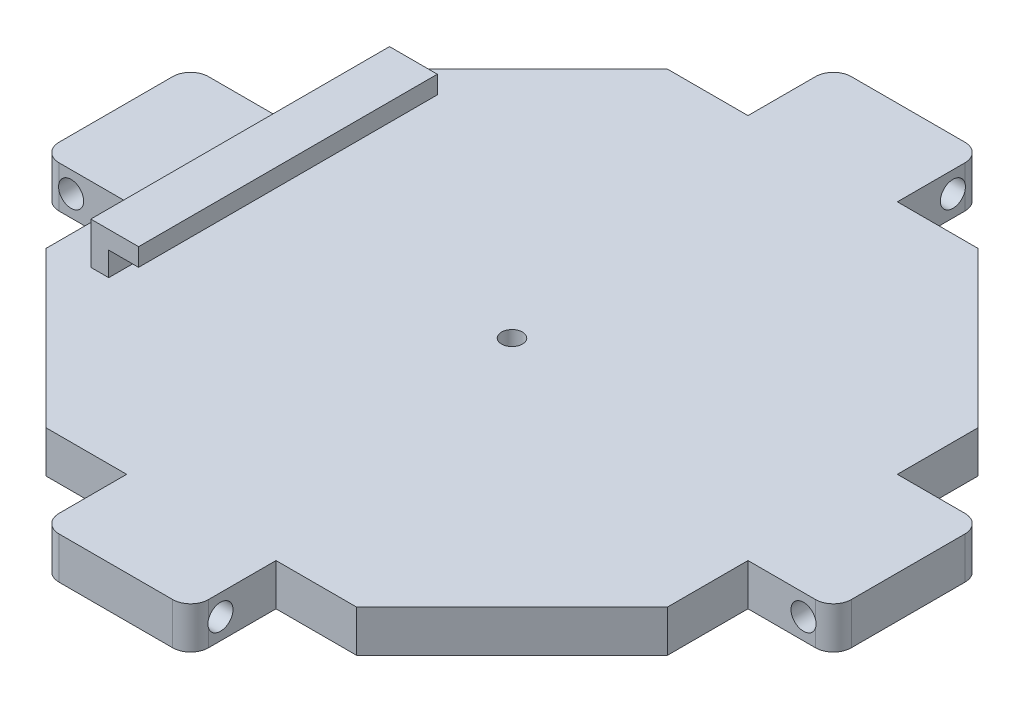
SolidWorks part; units mm, degrees
ref_plane "정면" through (0, 0, 0) normal (0, 0, 1) x (1, 0, 0)
ref_plane "윗면" through (0, 0, 0) normal (0, 1, 0) x (1, 0, 0)
ref_plane "우측면" through (0, 0, 0) normal (1, 0, 0) x (0, 0, -1)
sketch "스케치1" plane through (0, 0, 0) normal (0, 1, 0) x (1, 0, 0)
  line L0 (0, 0) -> (-27.1519, 0) construction
  line L1 (-39, 39) -> (39, 39)
  line L2 (-39, 39) -> (-39, -39)
  line L3 (-39, -39) -> (39, -39)
  line L4 (39, 39) -> (39, -39)
  line L5 (-39, 39) -> (39, -39) construction
  line L6 (-39, -39) -> (39, 39) construction
  line L7 (39, 0) -> (-66.3, 0) construction
  line L8 (-66.3, 0) -> (0, 39) construction
  line L9 (0, 39) -> (0, -39) construction
  line L10 (-26, 39) -> (-39, 26)
  line L11 (-39, -26) -> (-26, -39)
  line L12 (26, -39) -> (39, -26)
  line L13 (26, 39) -> (39, 26)
  line L14 (-26, -52) -> (26, -52)
  line L15 (26, -52) -> (52, -26)
  line L16 (52, -26) -> (52, 26)
  line L17 (52, 26) -> (26, 52)
  line L18 (26, 52) -> (-26, 52)
  line L19 (-26, 52) -> (-52, 26)
  line L20 (-52, 26) -> (-52, -26)
  line L21 (-52, -26) -> (-26, -52)
  line L22 (-52, 12.5) -> (-66.3, 12.5)
  line L23 (-66.3, 12.5) -> (-66.3, -12.5)
  line L24 (-66.3, -12.5) -> (-52, -12.5)
  line L25 (-12.5, -52) -> (-12.5, -66.3)
  line L26 (-12.5, -66.3) -> (12.5, -66.3)
  line L27 (12.5, -66.3) -> (12.5, -52)
  line L28 (52, -12.5) -> (66.3, -12.5)
  line L29 (66.3, -12.5) -> (66.3, 12.5)
  line L30 (66.3, 12.5) -> (52, 12.5)
  line L31 (-12.5, 52) -> (-12.5, 66.3)
  line L32 (-12.5, 66.3) -> (12.5, 66.3)
  line L33 (12.5, 66.3) -> (12.5, 52)
  point P0 (0, 0)
  dimension "D1" = 78
  dimension "D2" = 78
  dimension "D3" = 26
  dimension "D4" = 26
  dimension "D5" = 26
  dimension "D6" = 26
  dimension "D7" = 26
  dimension "D8" = 26
  dimension "D9" = 26
  dimension "D10" = 26
  dimension "D11" = 13
  dimension "D12" = 13
  dimension "D13" = 13
  dimension "D14" = 13
  dimension "D15" = 25
  dimension "D16" = 25
  dimension "D17" = 25
  dimension "D18" = 25
  dimension "D19" = 14.3
  dimension "D20" = 14.3
  dimension "D21" = 14.3
  dimension "D22" = 14.3
  dimension "D23" = 14.3
  dimension "D24" = 12.5
  dimension "D25" = 12.5
  dimension "D26" = 12.5
extrude "보스-돌출1" add sketch "스케치1" along normal blind 7 contours L18 L19 L1 L17 | L10 L1 L2 | L20 L21 L2 L19 | L23 L24 L20 L22 | L33 L32 L31 L18 | L1 L13 L4 | L16 L17 L4 L15 | L29 L30 L16 L28 | L12 L3 L4 | L3 L21 L14 L15 | L11 L2 L3 | L26 L27 L14 L25 region at (0, 0, -45.0667) region at (-34.6667, 0, -34.6667) region at (-45.0667, 0, 0) region at (34.6667, 0, -34.6667) region at (-34.6667, 0, 34.6667) region at (0, 0, -59.15) region at (-59.15, 0, 0) region at (45.0667, 0, 0) region at (0, 0, 45.0667) region at (34.6667, 0, 34.6667) region at (59.15, 0, 0) region at (0, 0, 59.15)
fillet "필렛1" radius 3 8 edges at (-12.5, 3.5, 66.3) (66.3, 3.5, 12.5) (66.3, 3.5, -12.5) (12.5, 3.5, -66.3) (-12.5, 3.5, -66.3) (-66.3, 3.5, -12.5) (-66.3, 3.5, 12.5) (12.5, 3.5, 66.3)
fillet "필렛3" radius 23 8 edges at (-39, 3.5, 26) (-26, 3.5, 39) (26, 3.5, 39) (39, 3.5, 26) (39, 3.5, -26) (26, 3.5, -39) (-26, 3.5, -39) (-39, 3.5, -26)
sketch "스케치6" plane through (0, 7, 0) normal (0, 1, 0) x (1, 0, 0)
  line L0 (-39, 16.4731) -> (-39, -16.4731) construction
  line L5 (16.4731, 39) -> (-16.4731, 39)
  line L6 (-39, 16.4731) -> (-39, -16.4731)
  line L7 (-16.4731, -39) -> (16.4731, -39)
  line L8 (39, -16.4731) -> (39, 16.4731)
  arc A0 (16.4731, 39) -> (32.4983, 32.4983) centre (16.4731, 16) cw
  arc A1 (32.4983, 32.4983) -> (39, 16.4731) centre (16, 16.4731) cw
  arc A2 (32.4983, -32.4983) -> (39, -16.4731) centre (16, -16.4731) ccw
  arc A3 (32.4983, -32.4983) -> (16.4731, -39) centre (16.4731, -16) cw
  arc A4 (-32.4983, -32.4983) -> (-16.4731, -39) centre (-16.4731, -16) ccw
  arc A5 (-32.4983, -32.4983) -> (-39, -16.4731) centre (-16, -16.4731) cw
  arc A6 (-32.4983, 32.4983) -> (-39, 16.4731) centre (-16, 16.4731) ccw
  arc A7 (-32.4983, 32.4983) -> (-39, 16.4731) centre (-16, 16.4731) ccw construction
  arc A8 (-32.4983, 32.4983) -> (-16.4731, 39) centre (-16.4731, 16) cw
extrude "보스-돌출2" add sketch "스케치6" against normal blind 7
sketch "스케치7" plane through (0, 7, 0) normal (0, 1, 0) x (1, 0, 0)
  circle A0 centre (0, 0) radius 1.75
  dimension "D1" = 3.5
extrude "컷-돌출5" cut sketch "스케치7" against normal through all
sketch "스케치9" plane through (0, 7, 0) normal (0, 1, 0) x (1, 0, 0)
  line L0 (108.4856, 0) -> (-108.4856, 0) construction
  line L1 (-45.5, 25) -> (-42.5, 25)
  line L2 (-45.5, 25) -> (-45.5, -25)
  line L4 (-42.5, 25) -> (-42.5, -25)
  line L5 (-45.5, -25) -> (-42.5, -25)
  dimension "D1" = 42.5
  dimension "D2" = 3
extrude "보스-돌출3" add sketch "스케치9" along normal blind 7
sketch "스케치10" plane through (-42.5, 0, 0) normal (1, 0, 0) x (0, 0, -1)
  line L0 (-25, 14) -> (-25, 7) construction
  line L1 (25, 14) -> (-25, 14)
  line L2 (25, 14) -> (25, 11)
  line L3 (25, 11) -> (-25, 11)
  line L4 (-25, 14) -> (-25, 11)
  dimension "D1" = 3
extrude "보스-돌출4" add sketch "스케치10" along normal blind 5
sketch "스케치11" plane through (0, 0, 12.5) normal (0, 0, 1) x (1, 0, 0)
  line L0 (-66.3, 0) -> (-66.3, 7) construction
  line L1 (-63.3, 7) -> (-52, 7) construction
  line L2 (66.3, 7) -> (66.3, 0) construction
  line L3 (52, 7) -> (63.3, 7) construction
  circle A0 centre (-61.3, 3.5) radius 2.1
  circle A1 centre (61.3, 3.5) radius 2.1
  dimension "D1" = 4.2
  dimension "D6" = 4.2
  dimension "D2" = 5
  dimension "D3" = 3.5
  dimension "D4" = 5
  dimension "D5" = 3.5
extrude "컷-돌출6" cut sketch "스케치11" against normal through all
sketch "스케치12" plane through (-12.5, 0, 0) normal (-1, 0, 0) x (0, 0, 1)
  line L0 (-66.3, 0) -> (-66.3, 7) construction
  line L1 (-52, 7) -> (-63.3, 7) construction
  line L2 (66.3, 7) -> (66.3, 0) construction
  line L3 (63.3, 0) -> (52, 0) construction
  circle A0 centre (-61.3, 3.5) radius 2.1
  circle A1 centre (61.3, 3.5) radius 2.1
  dimension "D3" = 4.2
  dimension "D4" = 4.2
  dimension "D1" = 5
  dimension "D2" = 3.5
  dimension "D5" = 5
  dimension "D6" = 3.5
extrude "컷-돌출7" cut sketch "스케치12" against normal through all
